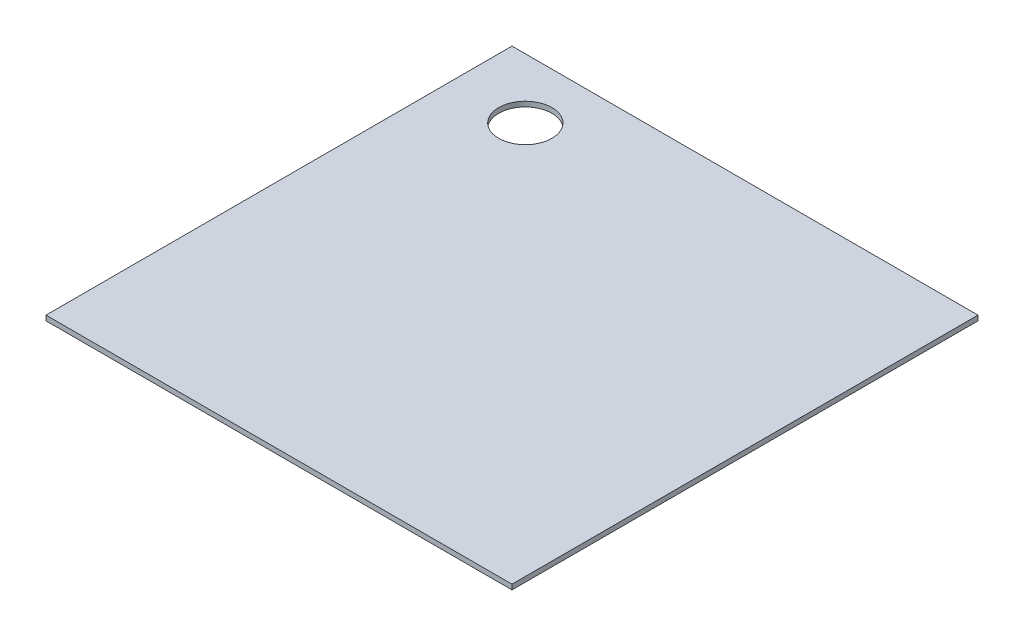
SolidWorks part; units mm, degrees
ref_plane "Front Plane" through (0, 0, 0) normal (0, 0, 1) x (1, 0, 0)
ref_plane "Top Plane" through (0, 0, 0) normal (0, 1, 0) x (1, 0, 0)
ref_plane "Right Plane" through (0, 0, 0) normal (1, 0, 0) x (0, 0, -1)
sketch "Sketch1" plane through (0, 0, 0) normal (0, 1, 0) x (1, 0, 0)
  line L1 (140, -140) -> (-140, -140)
  line L2 (140, -140) -> (140, 140)
  line L3 (140, 140) -> (-140, 140)
  line L4 (-140, -140) -> (-140, 140)
  line L5 (140, -140) -> (-140, 140) construction
  line L6 (140, 140) -> (-140, -140) construction
  circle A0 centre (-96, 104) radius 12.5 construction
  circle A2 centre (-96, 104) radius 16
  point P0 (0, 0)
  dimension "D2" = 25
  dimension "D4" = 44
  dimension "D5" = 36
  dimension "D3" = 32
  dimension "D1" = 280
extrude "Boss-Extrude1" add sketch "Sketch1" along normal mid plane 3
